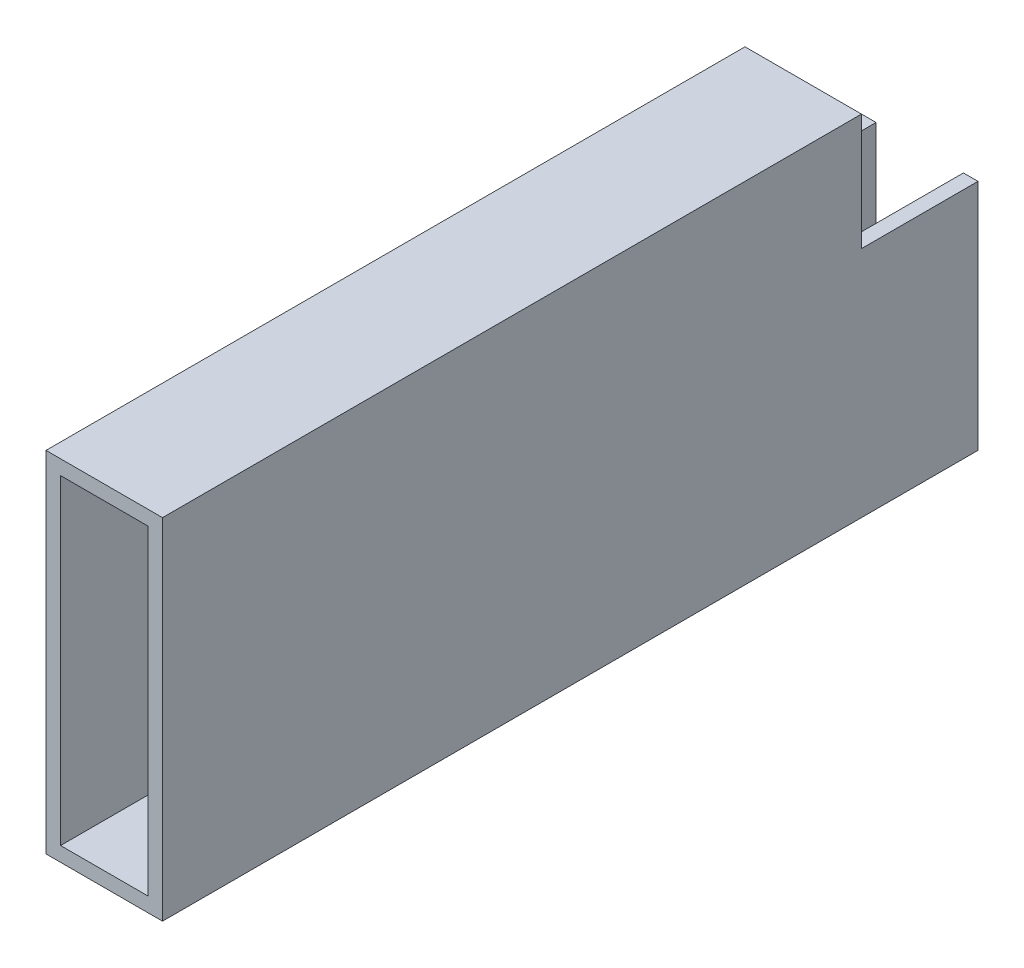
SolidWorks part; units mm, degrees
ref_plane "Front Plane" through (0, 0, 0) normal (0, 0, 1) x (1, 0, 0)
ref_plane "Top Plane" through (0, 0, 0) normal (0, 1, 0) x (1, 0, 0)
ref_plane "Right Plane" through (0, 0, 0) normal (1, 0, 0) x (0, 0, -1)
sketch "Sketch1" plane through (0, 0, 0) normal (0, 0, 1) x (1, 0, 0)
  line L1 (-12.7, -38.1) -> (12.7, -38.1)
  line L2 (-12.7, -38.1) -> (-12.7, 38.1)
  line L3 (-12.7, 38.1) -> (12.7, 38.1)
  line L4 (12.7, -38.1) -> (12.7, 38.1)
  line L5 (-12.7, -38.1) -> (12.7, 38.1) construction
  line L6 (-12.7, 38.1) -> (12.7, -38.1) construction
  point P0 (0, 0)
  dimension "D1" = 25.4
  dimension "D2" = 76.2
extrude "Boss-Extrude1" add sketch "Sketch1" along normal mid plane 177.8
shell "Shell1" thickness 3.175 removed face at (0, 0, -88.9) removed face at (0, 0, 88.9)
sketch "Sketch2" plane through (-12.7, 0, 0) normal (-1, 0, 0) x (0, 0, 1)
  line L1 (-88.9, 38.1) -> (-63.5, 38.1)
  line L2 (-88.9, 38.1) -> (-88.9, 12.7)
  line L3 (-88.9, 12.7) -> (-63.5, 12.7)
  line L4 (-63.5, 38.1) -> (-63.5, 12.7)
  dimension "D1" = 25.4
extrude "Cut-Extrude1" cut sketch "Sketch2" against normal through all
